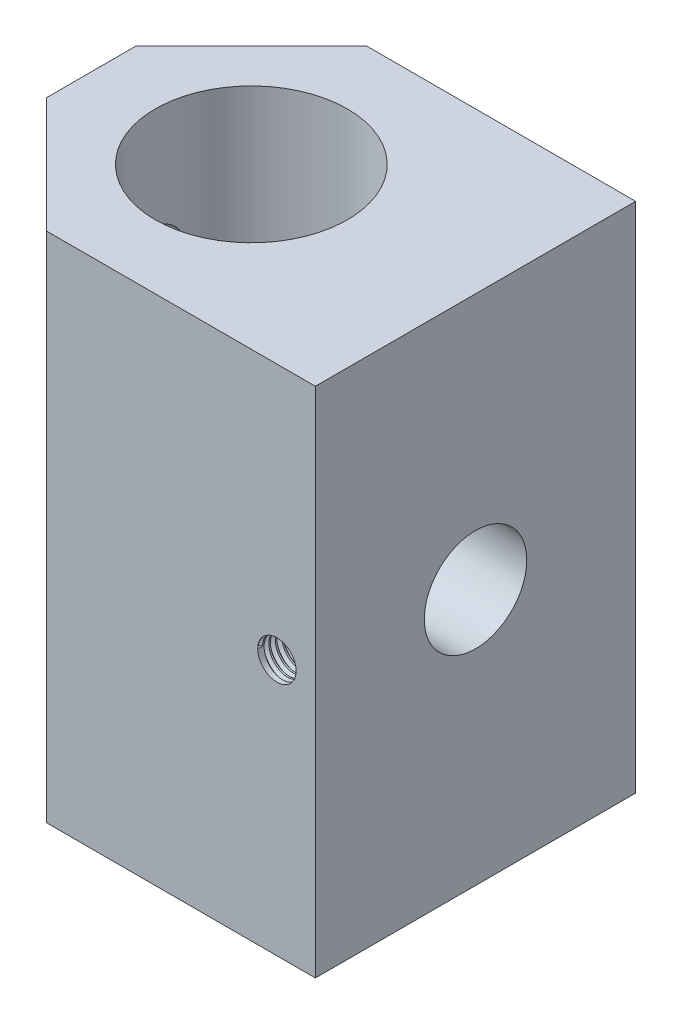
SolidWorks part; units mm, degrees
ref_plane "Front Plane" through (0, 0, 0) normal (0, 0, 1) x (1, 0, 0)
ref_plane "Top Plane" through (0, 0, 0) normal (0, 1, 0) x (1, 0, 0)
ref_plane "Right Plane" through (0, 0, 0) normal (1, 0, 0) x (0, 0, -1)
sketch "Sketch1" plane through (0, 0, 0) normal (0, 1, 0) x (1, 0, 0)
  line L1 (-15, -12.5) -> (15, -12.5)
  line L2 (-15, -12.5) -> (-15, 12.5)
  line L3 (-15, 12.5) -> (15, 12.5)
  line L4 (15, -12.5) -> (15, 12.5)
  line L5 (-15, -12.5) -> (15, 12.5) construction
  line L6 (-15, 12.5) -> (15, -12.5) construction
  circle A0 centre (-2.5, 0) radius 7.5
  point P0 (0, 0)
  point P9 (15, 0)
  dimension "D3" = 15
  dimension "D1" = 30
  dimension "D2" = 25
  dimension "D4" = 17.5
extrude "Boss-Extrude1" add sketch "Sketch1" along normal mid plane 40
sketch "Sketch2" plane through (15, 0, 0) normal (1, 0, 0) x (0, 0, -1)
  circle A0 centre (0, 0) radius 4
  dimension "D1" = 8
extrude "Cut-Extrude1" cut sketch "Sketch2" against normal blind 9 contours A0 region at (15, 0, 0)
sketch "Sketch3" plane through (-15, 0, 0) normal (-1, 0, 0) x (0, 0, 1)
  line L0 (-12.5, -20) -> (12.5, -20) construction
  circle A0 centre (0, -10) radius 2
  circle A1 centre (0, 10) radius 2
  point P10 (0, 0)
  dimension "D1" = 4
  dimension "D2" = 10
  dimension "D3" = 2
extrude "Cut-Extrude2" cut sketch "Sketch3" against normal blind 10
chamfer "Chamfer1" distance 9 angle 45 2 edges at (-15, 0, -12.5) (-15, 0, 12.5)
sketch "Sketch4" plane through (0, 0, 12.5) normal (0, 0, 1) x (1, 0, 0)
  line L0 (15, 20) -> (15, -20) construction
  circle A0 centre (12, 0) radius 1.5
  dimension "D1" = 3
  dimension "D2" = 3
extrude "Cut-Extrude3" cut sketch "Sketch4" against normal blind 11
thread "Thread1" pitch 0.5 method cut profile "Thread Profile1" start angle 0, offset 0, length 11, pitch 0.5, diameter 3
ref_plane "Plane1" through (10.5, 0, 12.5) normal (0, -1, 0) x (-1, 0, 0)
sketch "Thread Profile1" plane through (10.5, 0, 12.5) normal (0, -1, 0) x (-1, 0, 0)
  line L0 (0, 0) -> (0, 0.5) construction
  line L1 (0, 0) -> (0.2706, 0.1562)
  line L2 (0.2706, 0.1562) -> (0.2706, 0.2187)
  line L3 (0.2706, 0.2187) -> (0, 0.375)
  line L4 (0.2706, 0.1875) -> (0, 0.1875) construction
  line L11 (0, 0) -> (0, 0.375)
  point P2 (0, 0)
  dimension "Pitch" = 0.5
  dimension "Profile_Angle" = 60
  dimension "Profile_Land" = 0.0625
  dimension "Profile_Height" = 0.2706
